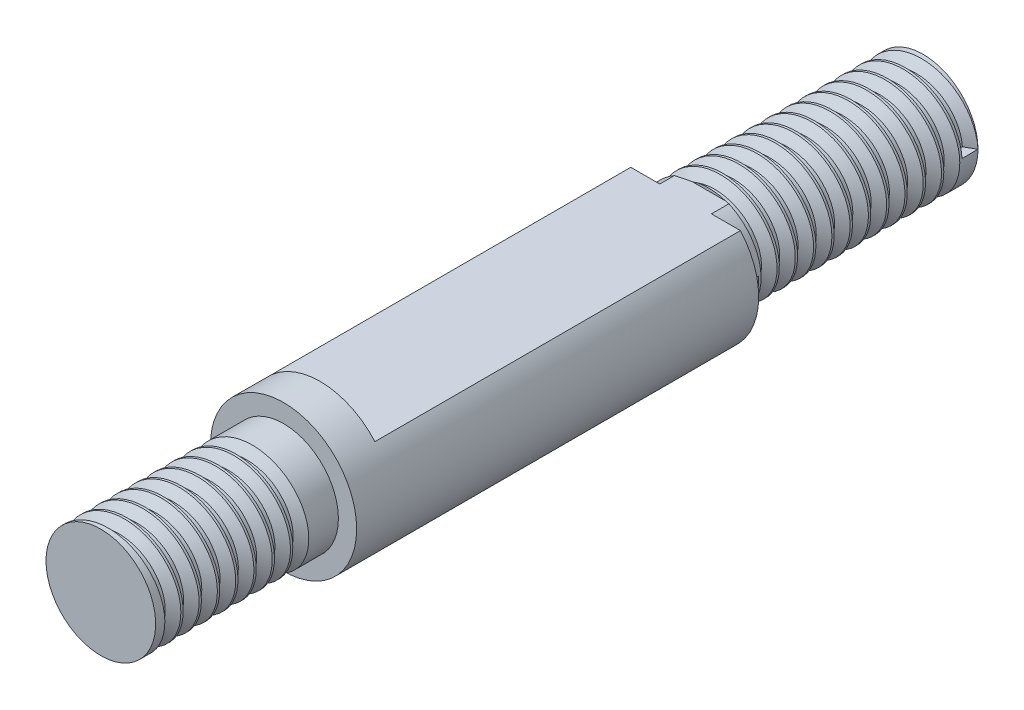
SolidWorks part; units mm, degrees
ref_plane "Alzado" through (0, 0, 0) normal (0, 0, 1) x (1, 0, 0)
ref_plane "Planta" through (0, 0, 0) normal (0, 1, 0) x (1, 0, 0)
ref_plane "Vista lateral" through (0, 0, 0) normal (1, 0, 0) x (0, 0, -1)
sketch "Croquis1" plane through (0, 0, 0) normal (0, 0, 1) x (1, 0, 0)
  circle A0 centre (0, 0) radius 3
  dimension "D1" = 6
extrude "Saliente-Extruir1" add sketch "Croquis1" along normal blind 45
ref_plane "Plano1" through (0, 0, 25) normal (0, 0, 1) x (1, 0, 0)
thread "Rosca1" pitch 1 method cut profile "Perfil de rosca1" start angle 0, offset 0, length 12, pitch 1, diameter 6
ref_plane "Plano2" through (3, 0, 0) normal (0, -1, 0) x (1, 0, 0)
sketch "Perfil de rosca1" plane through (3, 0, 0) normal (0, -1, 0) x (1, 0, 0)
  line L0 (0, 0) -> (0, 1) construction
  line L11 (0, 0) -> (0, 0.875)
  line L12 (0, 0.875) -> (-0.5413, 0.5625)
  line L13 (-0.5413, 0.5625) -> (-0.5413, 0.3125)
  line L15 (-0.5413, 0.3125) -> (0, 0)
  line L17 (-0.5413, 0.4375) -> (0, 0.4375) construction
  point P2 (0, 0)
  dimension "Pitch" = 1
  dimension "Profile_Angle" = 60
  dimension "Profile_Land" = 0.25
  dimension "Profile_Height" = 0.5413
thread "Rosca2" pitch 1 method cut profile "Perfil de rosca2" start angle 0, offset 0, length 8, pitch 1, diameter 6
ref_plane "Plano3" through (-3, 0, 45) normal (0, -1, 0) x (-1, 0, 0)
sketch "Perfil de rosca2" plane through (-3, 0, 45) normal (0, -1, 0) x (-1, 0, 0)
  line L0 (0, 0) -> (0, 1) construction
  line L11 (0, 0) -> (0, 0.875)
  line L12 (0, 0.875) -> (-0.5413, 0.5625)
  line L13 (-0.5413, 0.5625) -> (-0.5413, 0.3125)
  line L15 (-0.5413, 0.3125) -> (0, 0)
  line L17 (-0.5413, 0.4375) -> (0, 0.4375) construction
  point P2 (0, 0)
  dimension "Pitch" = 1
  dimension "Profile_Angle" = 60
  dimension "Profile_Land" = 0.25
  dimension "Profile_Height" = 0.5413
sketch "Croquis3" plane through (0, 0, 25) normal (0, 0, 1) x (1, 0, 0)
  circle A0 centre (0, 0) radius 4
  dimension "D1" = 8
extrude "Saliente-Extruir2" add sketch "Croquis3" along normal blind 10 and the other way blind 12
sketch "Croquis2" plane through (0, 0, 25) normal (0, 0, 1) x (1, 0, 0)
  line L1 (-3, 2.6458) -> (3, 2.6458)
  circle A3 centre (0, 0) radius 4 construction
  arc A4 (3, 2.6458) -> (-3, 2.6458) centre (0, 0) ccw
  dimension "D1" = 6
extrude "Cortar-Extruir1" cut sketch "Croquis2" against normal blind 13 and the other way blind 8
